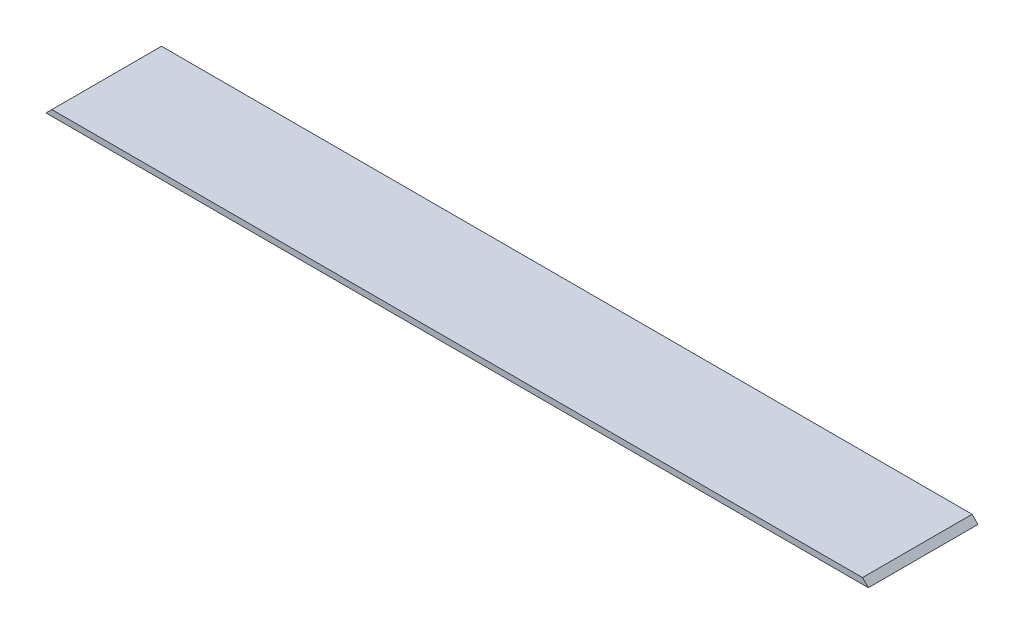
SolidWorks part; units mm, degrees
ref_plane "Front Plane" through (0, 0, 0) normal (0, 0, 1) x (1, 0, 0)
ref_plane "Top Plane" through (0, 0, 0) normal (0, 1, 0) x (1, 0, 0)
ref_plane "Right Plane" through (0, 0, 0) normal (1, 0, 0) x (0, 0, -1)
sketch "Sketch1" plane through (0, 0, 0) normal (0, 1, 0) x (1, 0, 0)
  line L1 (1333.5, -177.8) -> (-1333.5, -177.8)
  line L2 (1333.5, -177.8) -> (1333.5, 177.8)
  line L3 (1333.5, 177.8) -> (-1333.5, 177.8)
  line L4 (-1333.5, -177.8) -> (-1333.5, 177.8)
  line L5 (1333.5, -177.8) -> (-1333.5, 177.8) construction
  line L6 (1333.5, 177.8) -> (-1333.5, -177.8) construction
  point P0 (0, 0)
  dimension "D1" = 2667
  dimension "D2" = 355.6
extrude "Boss-Extrude1" add sketch "Sketch1" along normal mid plane 19.05
chamfer "Chamfer1" distance 19.05 angle 45 2 edges at (1333.5, 9.525, 0) (-1333.5, 9.525, 0)
